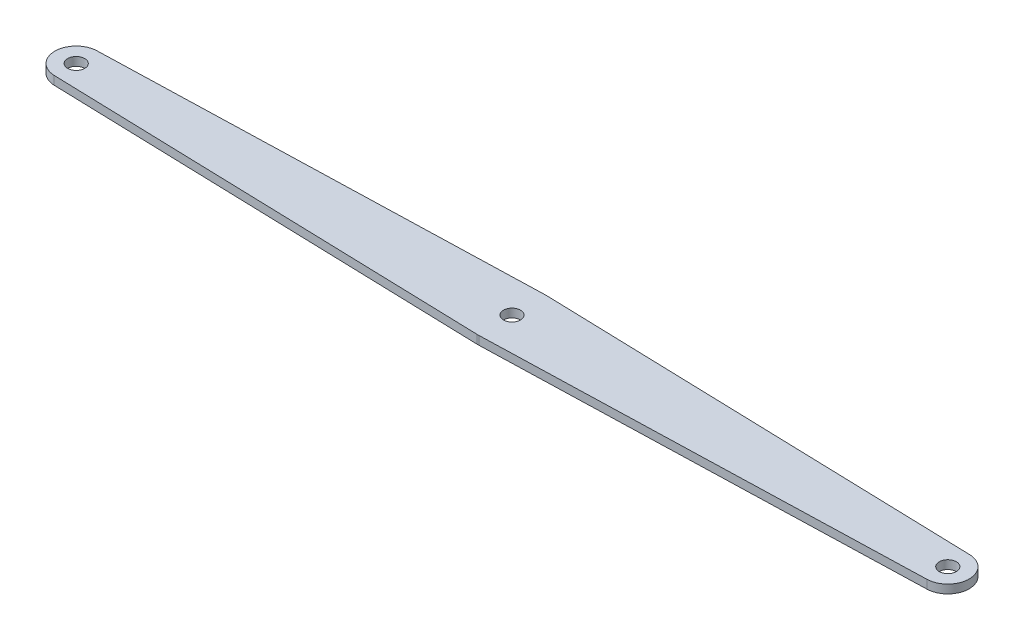
SolidWorks part; units mm, degrees
ref_plane "Спереди" through (0, 0, 0) normal (0, 0, 1) x (1, 0, 0)
ref_plane "Сверху" through (0, 0, 0) normal (0, 1, 0) x (1, 0, 0)
ref_plane "Справа" through (0, 0, 0) normal (1, 0, 0) x (0, 0, -1)
sketch "Эскиз1" plane through (0, 0, 0) normal (0, 1, 0) x (1, 0, 0)
  line L0 (-102, 0) -> (102, 0) construction
  line L1 (-102.1471, 4.9978) -> (-0.2353, 7.9965)
  line L2 (-102.1471, -4.9978) -> (-0.2353, -7.9965)
  line L3 (0.2353, 7.9965) -> (102.1471, 4.9978)
  line L5 (102.1471, -4.9978) -> (0.2353, -7.9965)
  arc A0 (0.2353, 7.9965) -> (-0.2353, 7.9965) centre (0, 0) ccw
  arc A1 (-102.1471, 4.9978) -> (-102.1471, -4.9978) centre (-102, 0) ccw
  arc A2 (102.1471, -4.9978) -> (102.1471, 4.9978) centre (102, 0) ccw
  arc A3 (-0.2353, -7.9965) -> (0.2353, -7.9965) centre (0, 0) ccw
  point P7 (0, 0)
  dimension "D2" = 8
  dimension "D3" = 5
  dimension "D1" = 204
extrude "тело" add sketch "Эскиз1" along normal blind 2
sketch "Эскиз2" plane through (0, 2, 0) normal (0, 1, 0) x (1, 0, 0)
  circle A0 centre (0, 0) radius 2
  dimension "D1" = 4
extrude "отверстие под ось вращения" cut sketch "Эскиз2" against normal through all
sketch "Эскиз3" plane through (0, 2, 0) normal (0, 1, 0) x (1, 0, 0)
  circle A0 centre (-102, 0) radius 2
  circle A1 centre (102, 0) radius 2
  dimension "D1" = 4
extrude "отверстие для крепления тягов" cut sketch "Эскиз3" against normal through all
